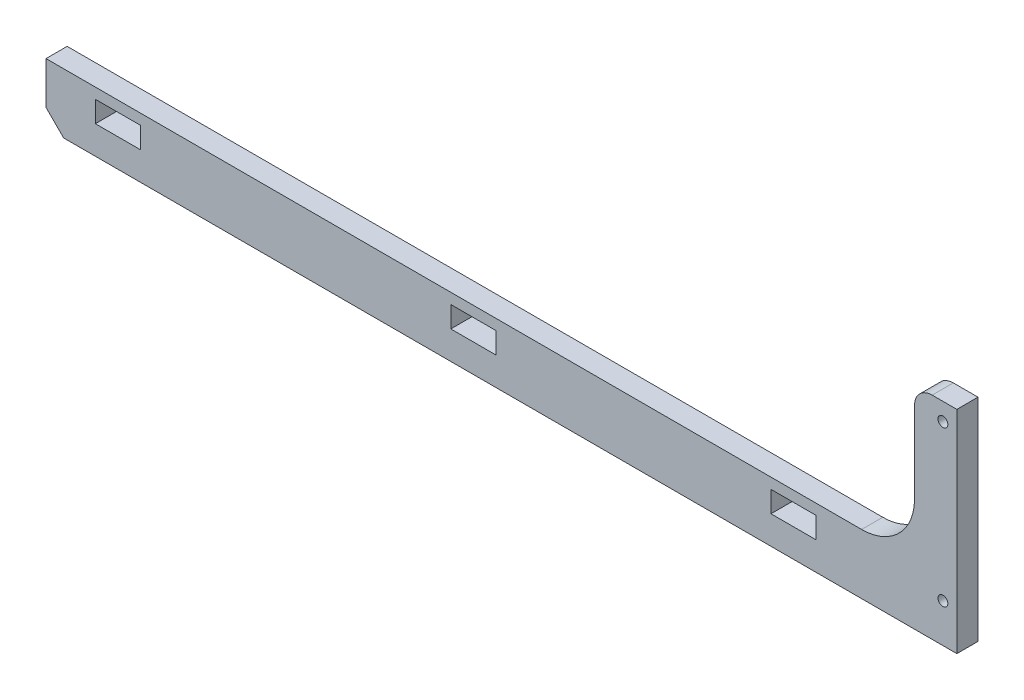
SolidWorks part; units mm, degrees
ref_plane "Front" through (0, 0, 0) normal (0, 0, 1) x (1, 0, 0)
ref_plane "Top" through (0, 0, 0) normal (0, 1, 0) x (1, 0, 0)
ref_plane "Right" through (0, 0, 0) normal (1, 0, 0) x (0, 0, -1)
sketch "Эскиз1" plane through (0, 0, 0) normal (0, 0, 1) x (1, 0, 0)
  line L0 (-165.3855, 0) -> (163.3727, 0) construction
  line L1 (-167.1826, 6) -> (64.1274, 6)
  line L2 (-167.1826, 6) -> (-167.1826, -6)
  line L4 (91.1274, 6) -> (91.1274, -11)
  line L5 (-162.1826, -11) -> (91.1274, -11)
  line L6 (-167.1826, -6) -> (-162.1826, -11)
  line L7 (51.2174, 3) -> (138.8459, 3) construction
  line L8 (91.1274, 6) -> (91.1274, 49)
  line L9 (91.1274, 49) -> (84.1274, 49)
  line L10 (51.2174, 42.1012) -> (51.2174, -60.2164) construction
  line L11 (-39.5826, 43.8022) -> (-39.5826, -70.5968) construction
  line L12 (38.4174, 3) -> (51.2174, 3)
  line L13 (38.4174, 3) -> (38.4174, -3)
  line L14 (38.4174, -3) -> (51.2174, -3)
  line L15 (51.2174, 3) -> (51.2174, -3)
  line L16 (38.4174, 3) -> (51.2174, -3) construction
  line L17 (38.4174, -3) -> (51.2174, 3) construction
  line L18 (-140.3826, 43.8022) -> (-140.3826, -35.6972) construction
  line L19 (-52.3826, 3) -> (-39.5826, 3)
  line L20 (-52.3826, 3) -> (-52.3826, -3)
  line L21 (-52.3826, -3) -> (-39.5826, -3)
  line L22 (-39.5826, 3) -> (-39.5826, -3)
  line L23 (-52.3826, 3) -> (-39.5826, -3) construction
  line L24 (-52.3826, -3) -> (-39.5826, 3) construction
  line L25 (79.1274, 44) -> (79.1274, 21)
  line L26 (-153.1826, 3) -> (-140.3826, 3)
  line L27 (-153.1826, 3) -> (-153.1826, -3)
  line L28 (-153.1826, -3) -> (-140.3826, -3)
  line L29 (-140.3826, 3) -> (-140.3826, -3)
  line L30 (-153.1826, 3) -> (-140.3826, -3) construction
  line L31 (-153.1826, -3) -> (-140.3826, 3) construction
  line L32 (87.1774, 0) -> (87.1774, 50.1588) construction
  arc A0 (79.1274, 21) -> (64.1274, 6) centre (64.1274, 21) cw
  arc A1 (84.1274, 49) -> (79.1274, 44) centre (84.1274, 44) ccw
  circle A2 centre (87.1774, 0) radius 1.4
  circle A3 centre (87.1774, 44) radius 1.4
  point P0 (0, 0)
  point P13 (44.8174, 0)
  point P20 (-45.9826, 0)
  point P27 (-146.7826, 0)
  point P38 (79.1274, 49)
  dimension "D15" = 15
  dimension "D16" = 5
  dimension "D17" = 2.8
  dimension "D18" = 3.95
  dimension "D19" = 2.8
  dimension "D2" = 39.91
  dimension "D3" = 12.8
  dimension "D4" = 6
  dimension "D5" = 90.8
  dimension "D6" = 12.8
  dimension "D7" = 6
  dimension "D8" = 100.8
  dimension "D9" = 6
  dimension "D10" = 12.8
  dimension "D11" = 3
  dimension "D12" = 46
  dimension "D13" = 17
  dimension "D14" = 12
extrude "Бобышка-Вытянуть1" add sketch "Эскиз1" along normal blind 6
